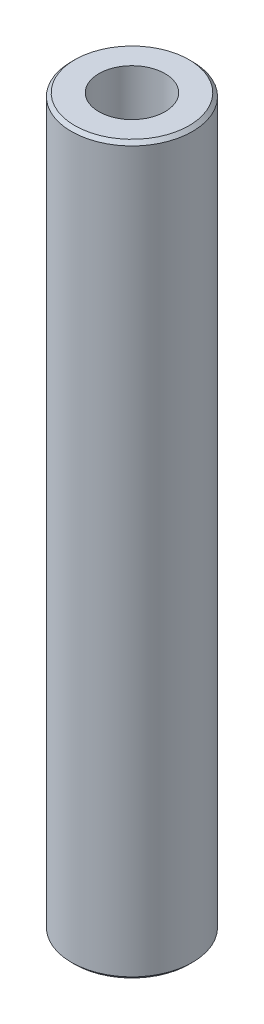
SolidWorks part; units mm, degrees
ref_plane "Front Plane" through (0, 0, 0) normal (0, 0, 1) x (1, 0, 0)
ref_plane "Top Plane" through (0, 0, 0) normal (0, 1, 0) x (1, 0, 0)
ref_plane "Right Plane" through (0, 0, 0) normal (1, 0, 0) x (0, 0, -1)
sketch "Sketch1" plane through (0, 0, 0) normal (0, 1, 0) x (1, 0, 0)
  circle A0 centre (0, 0) radius 50
  dimension "SHAFT_OD" = 100
extrude "Boss-Extrude1" add sketch "Sketch1" along normal blind 600
sketch "Sketch2" plane through (0, 0, 0) normal (0, 1, 0) x (1, 0, 0)
  circle A0 centre (0, 0) radius 27.3052
  dimension "BORE_D" = 54.6105
extrude "Cut-Extrude1" cut sketch "Sketch2" along normal through all
chamfer "Chamfer1" distance 2.793 angle 45 2 edges at (0, 600, 50) (0, 0, 50)
